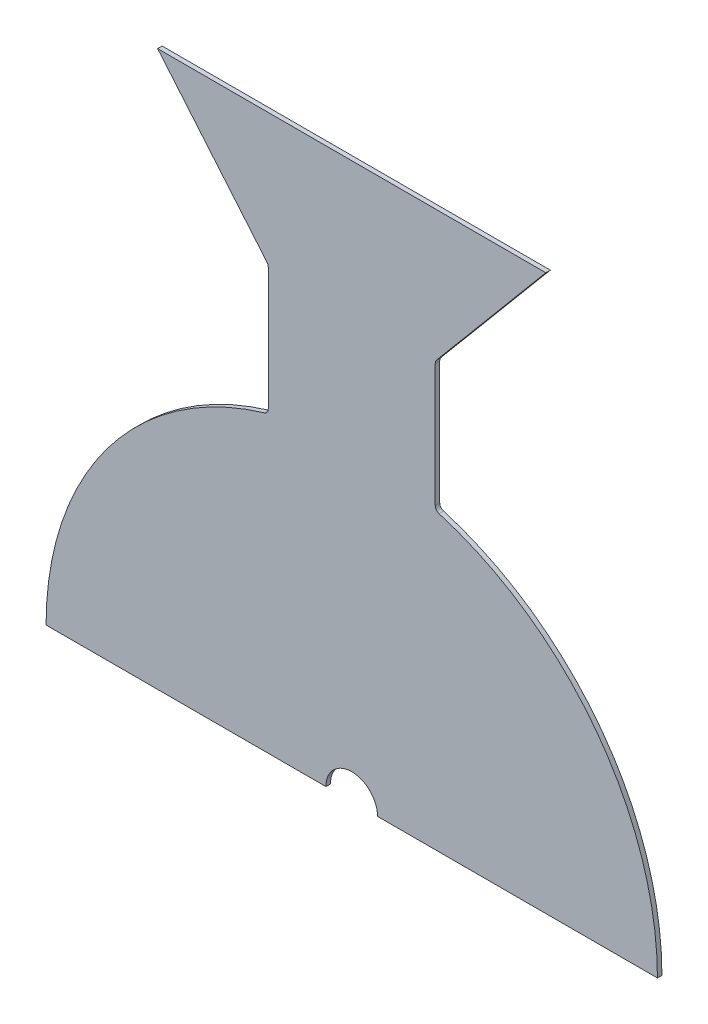
SolidWorks part; units mm, degrees
material "Plain Carbon Steel"
ref_plane "Front Plane" through (0, 0, 0) normal (0, 0, 1) x (1, 0, 0)
ref_plane "Top Plane" through (0, 0, 0) normal (0, 1, 0) x (1, 0, 0)
ref_plane "Right Plane" through (0, 0, 0) normal (1, 0, 0) x (0, 0, -1)
sketch "Sketch1" plane through (0, 0, 0) normal (0, 0, 1) x (1, 0, 0)
  line L0 (-180.4568, 0) -> (-15.24, 0)
  line L1 (0, 0) -> (0, 199.7416) construction
  line L3 (-49.2912, 0) -> (-15.24, 0) construction
  line L4 (-49.2912, 0) -> (-49.2912, 173.5945) construction
  line L5 (-49.2912, 173.5945) -> (49.2912, 173.5945) construction
  line L6 (49.2912, 0) -> (49.2912, 173.5945) construction
  line L9 (-49.2912, 173.5945) -> (-49.2912, 249.7945)
  line L10 (-49.2912, 249.7945) -> (-114.5985, 327.6246)
  line L11 (-114.5985, 327.6246) -> (114.5985, 327.6246)
  line L15 (49.2912, 173.5945) -> (49.2912, 249.7945)
  line L16 (49.2912, 249.7945) -> (114.5985, 327.6246)
  line L17 (-15.24, 0) -> (0, 0) construction
  line L18 (15.24, 0) -> (180.4568, 0)
  line L19 (-15.24, 0) -> (0, 0) construction
  line L20 (0, 0) -> (49.2912, 0) construction
  arc A0 (-180.4568, 0) -> (-49.2912, 173.5945) centre (0, 0) cw
  arc A1 (49.2912, 173.5945) -> (180.4568, 0) centre (0, 0) cw
  arc A2 (-15.24, 0) -> (15.24, 0) centre (0, 0) cw
  point P9 (0, 173.5945)
  point P21 (0, 327.6246)
  dimension "D2" = 180.4568
  dimension "D9" = 15.24
  dimension "D1" = 98.5825
  dimension "D4" = 76.2
  dimension "D5" = 101.6
  dimension "D6" = 140
base flange "Base-Flange1" sketch "Sketch1" thickness 2.6568 reverse thickness direction no parameters "D1"=0.7366
fillet "Fillet1" radius 3.175 4 edges at (49.2912, 249.7945, -1.3284) (-49.2912, 173.5945, -1.3284) (49.2912, 173.5945, -1.3284) (-49.2912, 249.7945, -1.3284)
sketch "Bend-Lines1" [suppressed] plane through (0, 0, 0) normal (0, 1, 0) x (1, 0, 0)
sketch "Bounding-Box1" [suppressed] plane through (0, 0, 0) normal (0, 1, 0) x (1, 0, 0)
sheet metal parameters "Sheet-Metal1" thickness 2.6568 parameters "D1"=0.7366
flat pattern "Flat-Pattern1" [suppressed]
sketch "Bend-Lines2" plane through (0, 0, 0) normal (0, 0, 1) x (1, 0, 0)
sketch3d "Bounding-Box2" [suppressed]
  line L0 (-180.4568, 0, 0) -> (180.4568, 0, 0) construction
  line L1 (-180.4568, 327.6246, 0) -> (180.4568, 327.6246, 0) construction
  line L2 (-180.4568, 0, 0) -> (-180.4568, 327.6246, 0) construction
  line L3 (180.4568, 0, 0) -> (180.4568, 327.6246, 0) construction
